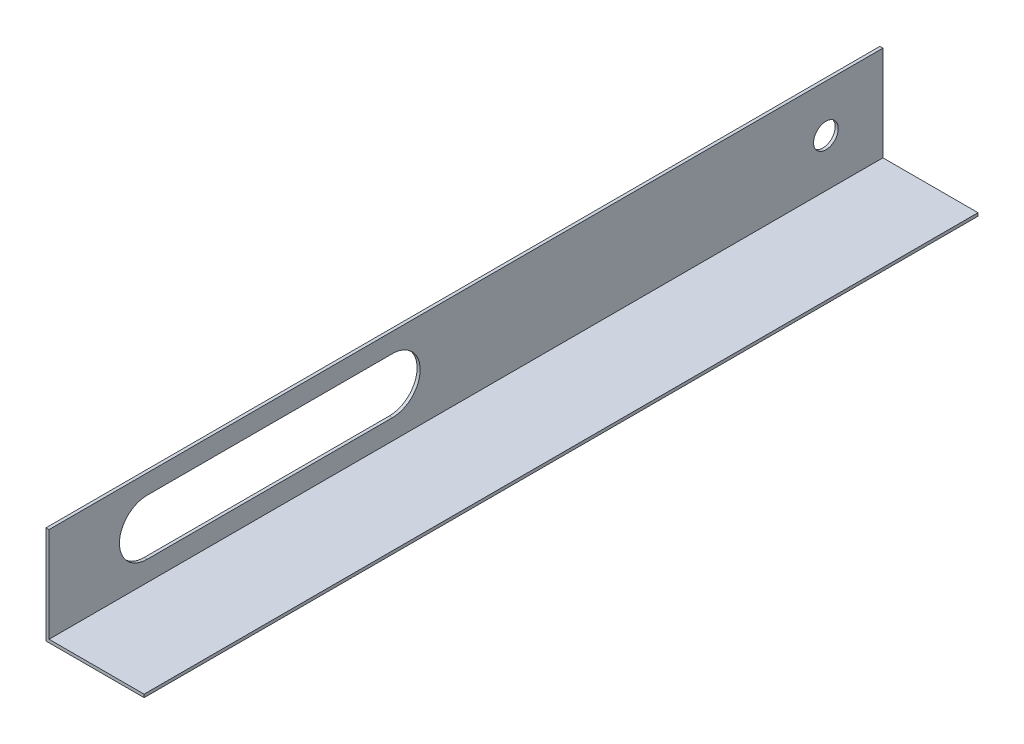
SolidWorks part; units mm, degrees
ref_plane "Front Plane" through (0, 0, 0) normal (0, 0, 1) x (1, 0, 0)
ref_plane "Top Plane" through (0, 0, 0) normal (0, 1, 0) x (1, 0, 0)
ref_plane "Right Plane" through (0, 0, 0) normal (1, 0, 0) x (0, 0, -1)
sketch "Sketch3" plane through (0, 0, 0) normal (0, 0, 1) x (1, 0, 0)
  line L0 (0, 0) -> (0, 49.2125)
  line L1 (0, 49.2125) -> (-1.5875, 49.2125)
  line L2 (-1.5875, 49.2125) -> (-1.5875, -1.5875)
  line L3 (-1.5875, -1.5875) -> (49.2125, -1.5875)
  line L4 (49.2125, -1.5875) -> (49.2125, 0)
  line L5 (49.2125, 0) -> (0, 0)
  dimension "D1" = 1.5875
  dimension "D2" = 1.5875
  dimension "D3" = 50.8
  dimension "D4" = 50.8
extrude "Boss-Extrude2" add sketch "Sketch3" along normal blind 431.8
sketch "Sketch6" plane through (0, 0, 0) normal (1, 0, 0) x (0, 0, -1)
  line L0 (-381, 24.8285) -> (-254, 24.8285) construction
  line L1 (-381, 39.1795) -> (-254, 39.1795)
  line L2 (-381, 10.4775) -> (-254, 10.4775)
  line L3 (-431.8, 0) -> (-431.8, 49.2125) construction
  line L5 (-431.8, 49.2125) -> (0, 49.2125) construction
  arc A0 (-381, 39.1795) -> (-381, 10.4775) centre (-381, 24.8285) ccw
  arc A1 (-254, 10.4775) -> (-254, 39.1795) centre (-254, 24.8285) ccw
  point P2 (-317.5, 24.8285)
  dimension "D3" = 50.8
  dimension "D1" = 28.702
  dimension "D2" = 127
  dimension "D4" = 24.384
extrude "Cut-Extrude3" cut sketch "Sketch6" against normal blind 127
sketch "Sketch7" plane through (0, 0, 0) normal (1, 0, 0) x (0, 0, -1)
  circle A0 centre (-29.5388, 24.7736) radius 6.3881
  dimension "D1" = 12.7762
extrude "Cut-Extrude4" cut sketch "Sketch7" against normal blind 127
